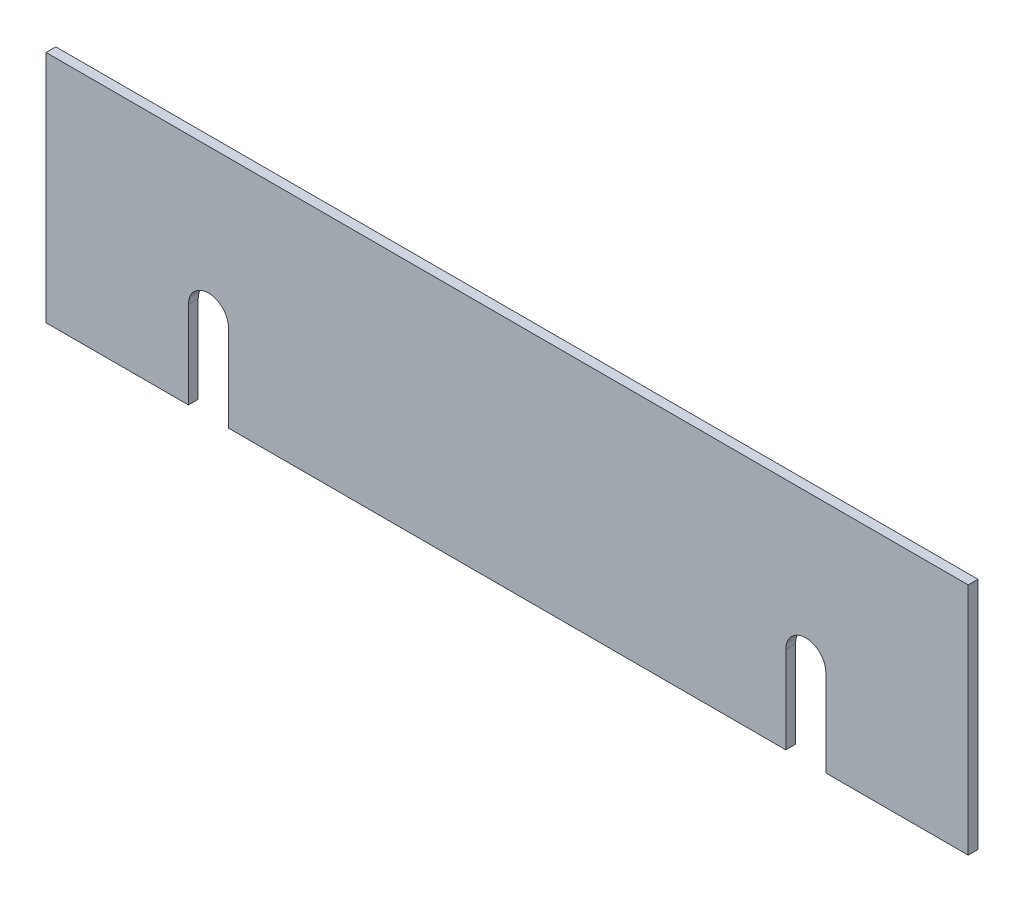
SolidWorks part; units mm, degrees
material "ABS"
ref_plane "X-Y Datum" through (0, 0, 0) normal (0, 0, 1) x (1, 0, 0)
ref_plane "X-Z Datum" through (0, 0, 0) normal (0, 1, 0) x (1, 0, 0)
ref_plane "Y-Z Datum" through (0, 0, 0) normal (1, 0, 0) x (0, 0, -1)
sketch "Sketch1" plane through (0, 0, 0) normal (0, 0, 1) x (1, 0, 0)
  line L1 (-149.85, 38.0375) -> (149.85, 38.0375)
  line L2 (-149.85, 38.0375) -> (-149.85, -38.0375)
  line L3 (-149.85, -38.0375) -> (149.85, -38.0375)
  line L4 (149.85, 38.0375) -> (149.85, -38.0375)
  line L5 (-149.85, 38.0375) -> (149.85, -38.0375) construction
  line L6 (-149.85, -38.0375) -> (149.85, 38.0375) construction
  point P0 (0, 0)
  dimension "D1" = 76.075
  dimension "D2" = 299.7
extrude "Boss-Extrude1" add sketch "Sketch1" along normal blind 3.175
sketch "Sketch3" plane through (0, 0, 0) normal (0, 0, -1) x (-1, 0, 0)
  line L0 (103.5631, -9.7625) -> (103.5631, -38.0375)
  line L1 (149.85, -38.0375) -> (-149.85, -38.0375) construction
  line L2 (90.5631, -9.7625) -> (90.5631, -38.0375)
  line L3 (149.85, -38.0375) -> (-149.85, -38.0375)
  line L4 (-103.5631, -9.7625) -> (-103.5631, -38.0375)
  line L5 (-90.5631, -9.7625) -> (-90.5631, -38.0375)
  circle A0 centre (97.0631, -9.7625) radius 5.75 construction
  circle A1 centre (-97.0631, -9.7625) radius 5.75 construction
  circle A2 centre (97.0631, -9.7625) radius 5.75 construction
  circle A3 centre (-97.0631, -9.7625) radius 5.75 construction
  circle A4 centre (97.0631, -9.7625) radius 6.5
  circle A5 centre (-97.0631, -9.7625) radius 6.5
  line M2 (-149.85, -38.0375) -> (149.85, -38.0375)
  dimension "D1" = 13
extrude "Cut-Extrude1" cut sketch "Sketch3" against normal through all contours A5 A3 | A3 | A5 L4 L3 L5 | A2 | A4 A2 | A4 L2 L0 M2 region at (97.0631, -26.4071, 0) region at (-97.0631, -9.7625, 0) region at (-97.0631, -26.4071, 0) region at (97.0631, -9.7625, 0)
